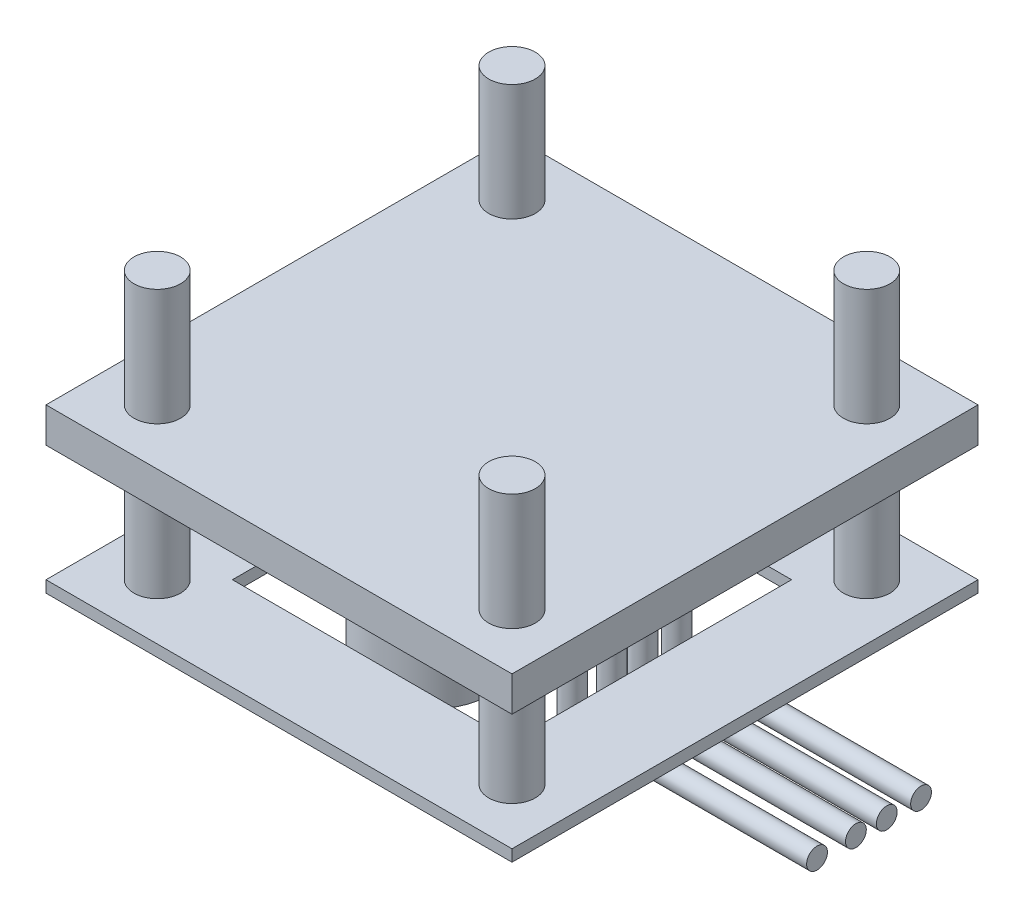
SolidWorks part; units mm, degrees
ref_plane "前视基准面" through (0, 0, 0) normal (0, 0, 1) x (1, 0, 0)
ref_plane "上视基准面" through (0, 0, 0) normal (0, 1, 0) x (1, 0, 0)
ref_plane "右视基准面" through (0, 0, 0) normal (1, 0, 0) x (0, 0, -1)
sketch "草图2" plane through (0, 0, 0) normal (0, 1, 0) x (1, 0, 0)
  line L0 (0, 0) -> (31.047, 0) construction
  line L1 (-12, -12) -> (12, -12)
  line L2 (-12, -12) -> (-12, 12)
  line L3 (-12, 12) -> (12, 12)
  line L4 (12, -12) -> (12, 12)
  line L5 (-12, -12) -> (12, 12) construction
  line L6 (-12, 12) -> (12, -12) construction
  line L7 (-20, -20) -> (20, -20)
  line L8 (-20, -20) -> (-20, 20)
  line L9 (-20, 20) -> (20, 20)
  line L10 (20, -20) -> (20, 20)
  line L11 (-20, -20) -> (20, 20) construction
  line L12 (-20, 20) -> (20, -20) construction
  line L13 (0, 0) -> (0, 17.7315) construction
  circle A0 centre (15.2248, 15.2248) radius 2
  circle A1 centre (-15.2248, -15.2248) radius 2
  circle A2 centre (15.2248, -15.2248) radius 2
  circle A3 centre (-15.2248, 15.2248) radius 2
  point P0 (0, 0)
  point P6 (0, 0)
  dimension "D5" = 4
  dimension "D1" = 24
  dimension "D2" = 24
  dimension "D3" = 40
  dimension "D4" = 40
  dimension "D6" = 21.5311
extrude "凸台-拉伸2" add sketch "草图2" along normal blind 1 contours L8 L9 L10 L7 | L2 L1 L4 L3
sketch "草图3" plane through (0, 0, 0) normal (0, 1, 0) x (1, 0, 0)
  line L7 (8, 6.0116) -> (11, 6.0116)
  line L8 (8, 6.0116) -> (8, -5.9884)
  line L9 (8, -5.9884) -> (11, -5.9884)
  line L10 (11, 6.0116) -> (11, -5.9884)
  circle A0 centre (-15.2248, -15.2248) radius 2 construction
  circle A1 centre (15.2248, -15.2248) radius 2 construction
  circle A2 centre (15.2248, 15.2248) radius 2 construction
  circle A3 centre (-15.2248, 15.2248) radius 2 construction
  circle A4 centre (-15.2248, -15.2248) radius 2
  circle A5 centre (15.2248, -15.2248) radius 2
  circle A6 centre (15.2248, 15.2248) radius 2
  circle A7 centre (-15.2248, 15.2248) radius 2
  circle A8 centre (-7, 0) radius 5.125
  point P27 (8, 0.0116)
  dimension "D1" = 10.25
  dimension "D2" = 8
  dimension "D5" = 12
  dimension "D6" = 3
extrude "切除-拉伸1" cut sketch "草图3" along normal blind 3
sketch "草图4" plane through (0, 0, 0) normal (0, 1, 0) x (1, 0, 0)
  line L0 (0, 0) -> (31.047, 0) construction
  circle A0 centre (3, 0) radius 2
  dimension "D1" = 4
  dimension "D2" = 3
sketch "草图9" plane through (0, 1, 0) normal (0, 1, 0) x (1, 0, 0)
  line L1 (20, -20) -> (-20, -20)
  line L2 (20, -20) -> (20, 20)
  line L3 (20, 20) -> (-20, 20)
  line L4 (-20, -20) -> (-20, 20)
extrude "凸台-拉伸4" add sketch "草图9" along normal blind 3 from offset 10 separate body
extrude "凸台-拉伸5" add sketch "草图3<3>" along normal blind 24 contours A4 | A7 | A6 | A5
sketch "草图3<3>" plane through (0, 0, 0) normal (0, 1, 0) x (1, 0, 0) same geometry as "草图3"
extrude "凸台-拉伸6" add sketch "草图2<8>" against normal blind 2 contours A0 | A3 | A1 | A2
sketch "草图2<8>" plane through (0, 0, 0) normal (0, 1, 0) x (1, 0, 0) same geometry as "草图2"
sketch "草图11" plane through (0, 11, 0) normal (0, -1, 0) x (1, 0, 0)
  line L1 (-14.325, -7.9352) -> (14.325, -7.9352)
  line L2 (-14.325, -7.9352) -> (-14.325, 7.9352)
  line L3 (-14.325, 7.9352) -> (14.325, 7.9352)
  line L4 (14.325, -7.9352) -> (14.325, 7.9352)
  line L5 (-14.325, -7.9352) -> (14.325, 7.9352) construction
  line L6 (-14.325, 7.9352) -> (14.325, -7.9352) construction
  point P0 (0, 0)
extrude "凸台-拉伸7" add sketch "草图11" along normal blind 2
sketch "草图12" plane through (0, 1, 0) normal (0, 1, 0) x (1, 0, 0)
  circle A0 centre (-7, 0) radius 5.125 construction
  circle A1 centre (-7, 0) radius 5.125
extrude "凸台-拉伸8" add sketch "草图12" along normal blind 10 and the other way blind 9.4969
sketch "草图13" plane through (0, 9, 0) normal (0, -1, 0) x (1, 0, 0)
  line L0 (11, 5.9884) -> (11, -6.0116) construction
  line L1 (11, 5.9884) -> (11, -6.0116)
  line L2 (11, -6.0116) -> (8, -6.0116) construction
  line L3 (8, 5.9884) -> (11, 5.9884) construction
  line L4 (14.325, -7.9352) -> (14.325, 7.9352)
  line L5 (14.325, 7.9352) -> (-14.325, 7.9352)
  line L6 (-14.325, 7.9352) -> (-14.325, -7.9352)
  line L7 (-14.325, -7.9352) -> (14.325, -7.9352)
  line L8 (14.325, -7.9352) -> (14.325, 7.9352)
  line L9 (14.325, 7.9352) -> (-14.325, 7.9352)
  line L10 (-14.325, 7.9352) -> (-14.325, -7.9352)
  line L11 (-14.325, -7.9352) -> (14.325, -7.9352)
  line L12 (8, -6.0116) -> (8, 5.9884) construction
  line L13 (11, -6.0116) -> (8, -6.0116)
  line L14 (11, 5.9884) -> (11, -6.0116)
  line L15 (8, 5.9884) -> (11, 5.9884)
  line L16 (8, -6.0116) -> (8, 5.9884)
  dimension "D1" = 0
extrude "凸台-拉伸9" add sketch "草图13" along normal blind 3 contours L16 L13 L1 L15 | L14 L1 region at (9.5, 9, -0.0116)
sketch "草图14" plane through (0, 6, 0) normal (0, -1, 0) x (1, 0, 0)
  line L1 (11, -6.0116) -> (8, -6.0116) construction
  circle A2 centre (9.6122, 1.0342) radius 0.9263
  circle A4 centre (9.5395, -4.5935) radius 0.9263
  circle A5 centre (9.6122, -1.6304) radius 0.9263
  circle A6 centre (9.5395, 4.3493) radius 0.9263
  dimension "D1" = 1.4181
extrude "凸台-拉伸10" add sketch "草图14" along normal blind 9
sketch "草图16" plane through (0, 0, 0) normal (1, 0, 0) x (0, 0, -1)
  circle A0 centre (-4.3167, -2.2841) radius 0.8937
  circle A1 centre (-0.9811, -2.2841) radius 0.8937
  circle A2 centre (1.6678, -2.2841) radius 0.8937
  circle A3 centre (4.611, -2.2841) radius 0.8937
extrude "凸台-拉伸11" add sketch "草图16" along normal blind 21 from offset 9.5
